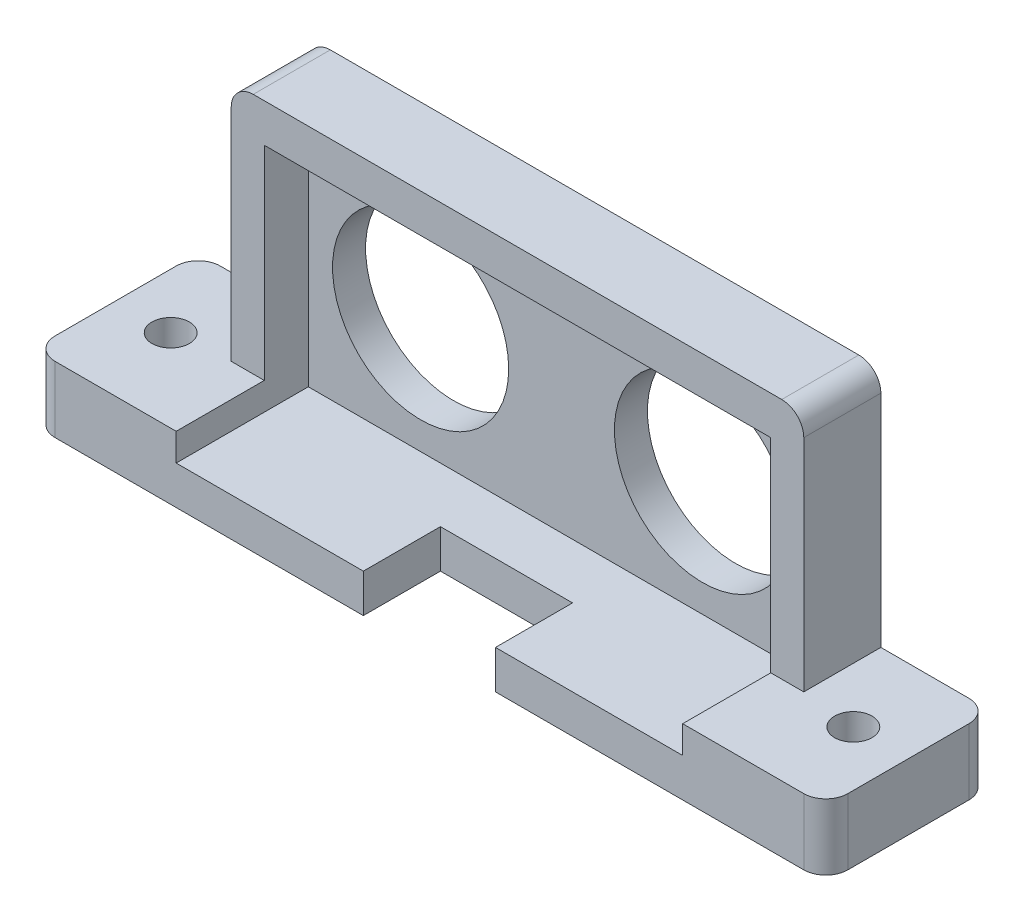
SolidWorks part; units mm, degrees
material "PLA"
ref_plane "Plan de face" through (0, 0, 0) normal (0, 0, 1) x (1, 0, 0)
ref_plane "Plan de dessus" through (0, 0, 0) normal (0, 1, 0) x (1, 0, 0)
ref_plane "Plan de droite" through (0, 0, 0) normal (1, 0, 0) x (0, 0, -1)
sketch "Esquisse1" plane through (0, 0, 0) normal (0, 0, 1) x (1, 0, 0)
  line L0 (36, 0) -> (-36, 0)
  line L1 (-36, 0) -> (36, 0) construction
  line L2 (-36, 0) -> (-36, 28) construction
  line L3 (-36, 28) -> (36, 28) construction
  line L4 (36, 0) -> (36, 28) construction
  line L5 (-36, 0) -> (-36, 6)
  line L6 (-36, 6) -> (-26, 6)
  line L7 (-26, 6) -> (-26, 28)
  line L8 (-26, 28) -> (26, 28)
  line L9 (26, 28) -> (26, 6)
  line L10 (26, 6) -> (36, 6)
  line L11 (36, 6) -> (36, 0)
  point P4 (0, 0)
  dimension "D1" = 72
  dimension "D2" = 28
  dimension "D3" = 10
  dimension "D4" = 6
  dimension "D5" = 6
  dimension "D6" = 10
extrude "Boss.-Extru.1" add sketch "Esquisse1" along normal blind 15
sketch "Esquisse2" plane through (0, 0, 15) normal (0, 0, 1) x (1, 0, 0)
  line L0 (0, 0) -> (0, 28) construction
  line L1 (-23, 24.5) -> (23, 24.5) construction
  line L2 (-23, 24.5) -> (-23, 3.5) construction
  line L3 (-23, 3.5) -> (23, 3.5) construction
  line L4 (23, 24.5) -> (23, 3.5) construction
  line L5 (26, 28) -> (-26, 28) construction
  line L6 (-23, 14) -> (23, 14) construction
  line L9 (-23, 24.5) -> (23, 24.5)
  line L10 (-23, 24.5) -> (-23, 3.5)
  line L11 (-23, 3.5) -> (23, 3.5)
  line L12 (23, 24.5) -> (23, 3.5)
  point P4 (0, 3.5)
  point P9 (0, 14)
  dimension "D1" = 46
  dimension "D2" = 21
extrude "Enlèv. mat.-Extru.1" cut sketch "Esquisse2" against normal offset from surface (12 mm away) 3 up to face at (0, 10, 0)
sketch "Esquisse4" plane through (0, 0, 3) normal (0, 0, 1) x (1, 0, 0)
  line L0 (-4.8, 14) -> (4.8, 14) construction
  line L1 (0, 0) -> (0, 28) construction
  line L2 (-36, 0) -> (36, 0) construction
  line L3 (26, 28) -> (-26, 28) construction
  circle A0 centre (-12.8, 14) radius 8
  circle A1 centre (12.8, 14) radius 8
  point P12 (0, 14)
  point P13 (0, 14)
  dimension "D1" = 16
  dimension "D2" = 16
  dimension "D3" = 9.6
extrude "Enlèv. mat.-Extru.2" cut sketch "Esquisse4" against normal blind 3
sketch "Esquisse5" plane through (0, 0, 0) normal (0, -1, 0) x (1, 0, 0)
  line L0 (-36, 15) -> (36, 15) construction
  line L1 (-6, 15) -> (6, 15)
  line L2 (-6, 15) -> (-6, 8)
  line L3 (-6, 8) -> (6, 8)
  line L4 (6, 15) -> (6, 8)
  line L5 (0, 0) -> (0, 15) construction
  point P9 (0, 15)
  dimension "D1" = 12
  dimension "D2" = 7
extrude "Enlèv. mat.-Extru.3" cut sketch "Esquisse5" against normal up to surface (28 mm away) up to face at (0, 28, 7.5)
fillet "Congé1" radius 2 6 edges at (-36, 3, 0) (36, 3, 0) (36, 3, 15) (-36, 3, 15) (-26, 28, 7.5) (26, 28, 7.5)
sketch "Esquisse6" plane through (0, 6, 0) normal (0, 1, 0) x (1, 0, 0)
  line L0 (-36, -7.5) -> (36, -7.5) construction
  line L1 (-36, -13) -> (-36, -2) construction
  line L2 (36, -13) -> (36, -2) construction
  circle A0 centre (31, -7.5) radius 1
  circle A1 centre (-31, -7.5) radius 1
  dimension "D1" = 2
  dimension "D2" = 2
  dimension "D3" = 5
  dimension "D4" = 5
hole_wizard "Dégagement M31" positions "Esquisse7" profile "Esquisse9" hole size "M3" standard "ISO" end condition through all
sketch "Esquisse7" plane through (0, 6, 0) normal (0, 1, 0) x (1, 0, 0)
  point P0 (-31, -7.5)
  point P3 (31, -7.5)
sketch "Esquisse9" plane through (-31, 6, 7.5) normal (1, 0, 0) x (0, 0, 1)
  line L0 (0, 0) -> (0, 6)
  line L1 (0, 6) -> (1.7, 6)
  line L2 (1.7, 6) -> (1.7, 0)
  line L5 (1.7, 0) -> (0, 0)
  line L11 (0, -6.35) -> (0, 107.95) construction
  dimension "Diamètre du perçage jusqu'au prochain" = 3.4
  dimension "Profondeur du perçage jusqu'au prochain" = 6
sketch "Esquisse10" plane through (26, 0, 0) normal (1, 0, 0) x (0, 0, -1)
  line L1 (-15, 6) -> (-7, 6)
  line L2 (-15, 6) -> (-15, 31)
  line L3 (-15, 31) -> (-7, 31)
  line L4 (-7, 6) -> (-7, 31)
  dimension "D1" = 25
  dimension "D2" = 8
extrude "Enlèv. mat.-Extru.4" cut sketch "Esquisse10" against normal up to surface (52 mm away) up to face at (-26, 16, 7.5)
